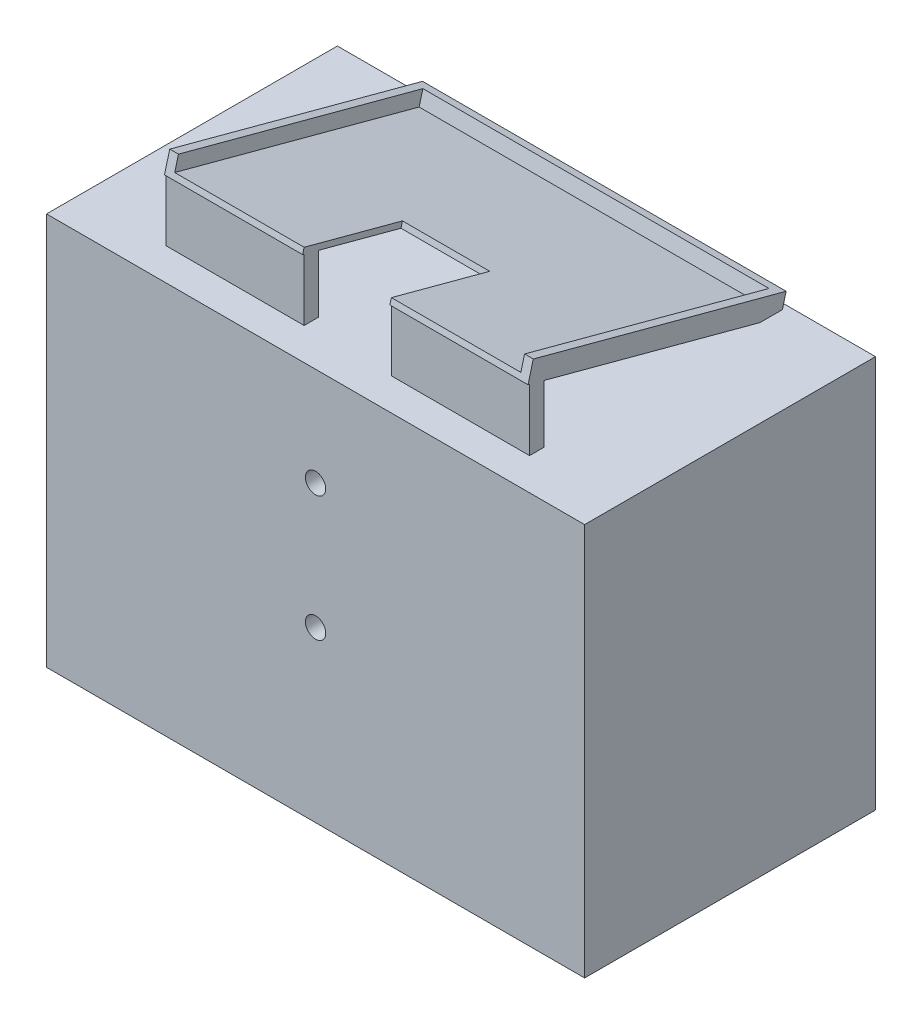
SolidWorks part; units mm, degrees
ref_plane "Plano frontal" through (0, 0, 0) normal (0, 0, 1) x (1, 0, 0)
ref_plane "Plano superior" through (0, 0, 0) normal (0, 1, 0) x (1, 0, 0)
ref_plane "Plano direito" through (0, 0, 0) normal (1, 0, 0) x (0, 0, -1)
sketch "Esboço1" plane through (0, 0, 0) normal (0, 0, 1) x (1, 0, 0)
  line L1 (-79.0518, 44.7141) -> (105.9482, 44.7141)
  line L2 (-79.0518, 44.7141) -> (-79.0518, -90.2859)
  line L3 (-79.0518, -90.2859) -> (105.9482, -90.2859)
  line L4 (105.9482, 44.7141) -> (105.9482, -90.2859)
  dimension "D1" = 185
  dimension "D2" = 135
extrude "Ressalto-extrusão1" add sketch "Esboço1" along normal blind 5
extrude "Ressalto-extrusão4" add sketch "Esboço1<2>" along normal blind 5 from offset 95 separate body
sketch "Esboço1<2>" plane through (0, 0, 0) normal (0, 0, 1) x (1, 0, 0) same geometry as "Esboço1"
sketch "Esboço3" plane through (0, 44.7141, 0) normal (0, 1, 0) x (1, 0, 0)
  line L1 (-79.0518, 0) -> (105.9482, 0)
  line L2 (-79.0518, 0) -> (-79.0518, -100)
  line L3 (-79.0518, -100) -> (105.9482, -100)
  line L4 (105.9482, 0) -> (105.9482, -100)
extrude "Ressalto-extrusão5" add sketch "Esboço3" against normal blind 5
sketch "Esboço4" plane through (-79.0518, 0, 0) normal (-1, 0, 0) x (0, 0, 1)
  line L1 (100, 44.7141) -> (0, 44.7141)
  line L2 (100, 44.7141) -> (100, -90.2859)
  line L3 (100, -90.2859) -> (0, -90.2859)
  line L4 (0, 44.7141) -> (0, -90.2859)
extrude "Ressalto-extrusão6" add sketch "Esboço4" against normal blind 5
extrude "Ressalto-extrusão7" add sketch "Esboço4<3>" along normal blind 5 from offset 185 offset against normal yes
sketch "Esboço4<3>" plane through (-79.0518, 0, 0) normal (-1, 0, 0) x (0, 0, 1) same geometry as "Esboço4"
sketch "Esboço8" plane through (0, 0, 100) normal (0, 0, 1) x (1, 0, 0)
  line L0 (105.9482, -90.2859) -> (105.9482, 44.7141) construction
  line L1 (-79.0518, 44.7141) -> (105.9482, 44.7141) construction
  circle A0 centre (13.4482, 10.8363) radius 3.5
  circle A1 centre (13.4482, -32.1637) radius 3.5
  dimension "D1" = 43
  dimension "D4" = 7
  dimension "D5" = 7
  dimension "D2" = 92.5
  dimension "D3" = 33.8778
extrude "Corte-extrusão1" cut sketch "Esboço8" against normal blind 10
sketch "Esboço10" plane through (0, 0, 0) normal (0, 1, 0) x (1, 0, 0)
  line L0 (100.9482, -55) -> (92.9482, -55)
  line L1 (100.9482, -5) -> (100.9482, -95) construction
  line L2 (92.9482, -43) -> (100.9482, -43)
  line L4 (100.9482, -43) -> (100.9482, -55)
  line L5 (13.4482, -130.4655) -> (13.4482, 35.3762) construction
  line L6 (105.9482, -100) -> (105.9482, 0) construction
  line L8 (-74.0518, -43) -> (-74.0518, -55)
  line L9 (-66.0518, -43) -> (-74.0518, -43)
  line L10 (-74.0518, -55) -> (-66.0518, -55)
  line L11 (-74.0518, -95) -> (100.9482, -95) construction
  arc A0 (92.9482, -43) -> (92.9482, -55) centre (92.9482, -49) ccw
  circle A1 centre (92.9482, -49) radius 2.5
  circle A2 centre (-66.0518, -49) radius 2.5
  arc A3 (-66.0518, -43) -> (-66.0518, -55) centre (-66.0518, -49) cw
  dimension "D1" = 12
  dimension "D3" = 5
  dimension "D2" = 8
  dimension "D4" = 92.5
  dimension "D5" = 40
extrude "Ressalto-extrusão10" add sketch "Esboço10" against normal blind 7 from offset 83.2 offset against normal yes
sketch "Esboço11" plane through (0, -90.2, 0) normal (0, -1, 0) x (1, 0, 0)
  line L0 (13.4482, 140.1948) -> (13.4482, -45.1427) construction
  line L1 (-61.7596, 51.5647) -> (-66.1267, 53.9994)
  line L2 (-66.1267, 53.9994) -> (-70.4189, 51.4348)
  line L3 (-70.4189, 51.4348) -> (-70.3439, 46.4353)
  line L4 (-70.3439, 46.4353) -> (-65.9768, 44.0006)
  line L5 (-65.9768, 44.0006) -> (-61.6846, 46.5652)
  line L6 (-61.6846, 46.5652) -> (-61.7596, 51.5647)
  line L7 (-79.0518, 100) -> (-79.0518, 0) construction
  line L8 (88.5811, 46.5652) -> (88.6561, 51.5647)
  line L9 (92.8733, 44.0006) -> (88.5811, 46.5652)
  line L10 (97.2404, 46.4353) -> (92.8733, 44.0006)
  line L11 (97.3154, 51.4348) -> (97.2404, 46.4353)
  line L12 (93.0232, 53.9994) -> (97.3154, 51.4348)
  line L13 (88.6561, 51.5647) -> (93.0232, 53.9994)
  circle A2 centre (-66.0518, 49) radius 4.3301 construction
  circle A3 centre (92.9482, 49) radius 4.3301 construction
  dimension "D1" = 5
  dimension "D2" = 92.5
extrude "Corte-extrusão2" cut sketch "Esboço11" against normal blind 6 from offset 2 offset against normal yes
sketch "Esboço12" plane through (-79.0518, 0, 0) normal (-1, 0, 0) x (0, 0, 1)
  line L0 (100, 44.7141) -> (0, 44.7141) construction
  line L1 (0, 44.7141) -> (0, -90.2859) construction
  circle A0 centre (25, -5.2859) radius 3.5
  dimension "D1" = 7
  dimension "D2" = 50
  dimension "D3" = 25
extrude "Corte-extrusão4" cut sketch "Esboço12" against normal blind 6
sketch "Esboço13" plane through (-74.0518, 0, 0) normal (1, 0, 0) x (0, 0, -1)
  line L1 (-40, 14.7141) -> (-10, 14.7141)
  line L2 (-40, 14.7141) -> (-40, -25.2859)
  line L3 (-40, -25.2859) -> (-10, -25.2859)
  line L4 (-10, 14.7141) -> (-10, -25.2859)
  circle A0 centre (-25, -5.2859) radius 3.5 construction
  dimension "D3" = 20
  dimension "D4" = 15
  dimension "D1" = 30
  dimension "D2" = 40
extrude "Corte-extrusão5" cut sketch "Esboço13" against normal blind 2
sketch "Esboço15" plane through (105.9482, 0, 0) normal (1, 0, 0) x (0, 0, -1)
  line L1 (-83.9333, 66.6681) -> (-83.9333, 44.7141)
  line L5 (-88.9333, 44.7141) -> (-88.9333, 68.0078)
  line L6 (-100, 44.7141) -> (0, 44.7141) construction
  line L8 (-88.9333, 44.7141) -> (-83.9333, 44.7141)
  line L9 (-83.9333, 66.6681) -> (-88.9333, 68.0078)
  dimension "D1" = 15
  dimension "D2" = 11.0667
  dimension "D3" = 5
extrude "Ressalto-extrusão15" add sketch "Esboço15" against normal blind 125 from offset 30 offset against normal yes
sketch3d "3DSketch2"
  point P0 (-1.4992, 66.5642, 83.5458)
sketch3d "3DSketch3"
  point P0 (26.871, 66.84, 84.5748)
ref_plane "Plano3" through (0, 41.2188, -11.0446) normal (0, 0.9659, -0.2588) x (1, 0, 0)
sketch "Esboço20" plane through (0, 41.2188, -11.0446) normal (0, 0.9659, -0.2588) x (1, 0, 0)
  line L0 (105.9482, -11.5729) -> (-79.0518, -11.5729) construction
  line L1 (-49.0518, -103.5047) -> (75.9482, -103.5047)
  line L2 (-49.0518, -103.5047) -> (-49.0518, -11.5729)
  line L3 (-49.0518, -11.5729) -> (75.9482, -11.5729)
  line L4 (75.9482, -103.5047) -> (75.9482, -11.5729)
  dimension "D1" = 125
extrude "Ressalto-extrusão20" add sketch "Esboço20" against normal blind 2
sketch "Esboço21" plane through (0, 41.2188, -11.0446) normal (0, 0.9659, -0.2588) x (1, 0, 0)
  line L0 (-49.0518, -103.5047) -> (75.9482, -103.5047) construction
  line L1 (75.9482, -13.5047) -> (-49.0518, -13.5047)
  line L2 (75.9482, -13.5047) -> (75.9482, -16.5047)
  line L3 (72.9482, -16.5047) -> (-46.0518, -16.5047)
  line L4 (-49.0518, -13.5047) -> (-49.0518, -16.5047)
  line L6 (-49.0518, -16.5047) -> (-49.0518, -103.5047)
  line L7 (-49.0518, -103.5047) -> (-46.0518, -103.5047)
  line L8 (-46.0518, -16.5047) -> (-46.0518, -103.5047)
  line L10 (75.9482, -103.5047) -> (72.9482, -103.5047)
  line L11 (75.9482, -103.5047) -> (75.9482, -16.5047)
  line L13 (72.9482, -103.5047) -> (72.9482, -16.5047)
  dimension "D1" = 3
  dimension "D2" = 3
  dimension "D3" = 3
extrude "Ressalto-extrusão21" add sketch "Esboço21" along normal blind 5
sketch "Esboço22" plane through (0, 41.2188, -11.0446) normal (0, 0.9659, -0.2588) x (1, 0, 0)
  line L0 (-46.0518, -103.5047) -> (72.9482, -103.5047) construction
  line L1 (28.4482, -103.5047) -> (-1.5518, -103.5047)
  line L2 (28.4482, -103.5047) -> (28.4482, -68.5047)
  line L3 (28.4482, -68.5047) -> (-1.5518, -68.5047)
  line L4 (-1.5518, -103.5047) -> (-1.5518, -68.5047)
  line L5 (75.9482, -16.5047) -> (75.9482, -103.5047) construction
  line L6 (-49.0518, -16.5047) -> (-49.0518, -103.5047) construction
  dimension "D1" = 47.5
  dimension "D2" = 47.5
  dimension "D3" = 35
extrude "Corte-extrusão6" cut sketch "Esboço22" against normal blind 2
sketch "Esboço23" plane through (0, 0, 88.9333) normal (0, 0, 1) x (1, 0, 0)
  line L0 (-49.0518, 44.7141) -> (75.9482, 44.7141) construction
  line L1 (-1.5518, 65.9373) -> (28.4482, 65.9373)
  line L2 (-1.5518, 65.9373) -> (-1.5518, 44.7141)
  line L3 (-1.5518, 44.7141) -> (28.4482, 44.7141)
  line L4 (28.4482, 65.9373) -> (28.4482, 44.7141)
  dimension "D1" = 30
extrude "Corte-extrusão7" cut sketch "Esboço23" against normal blind 5
